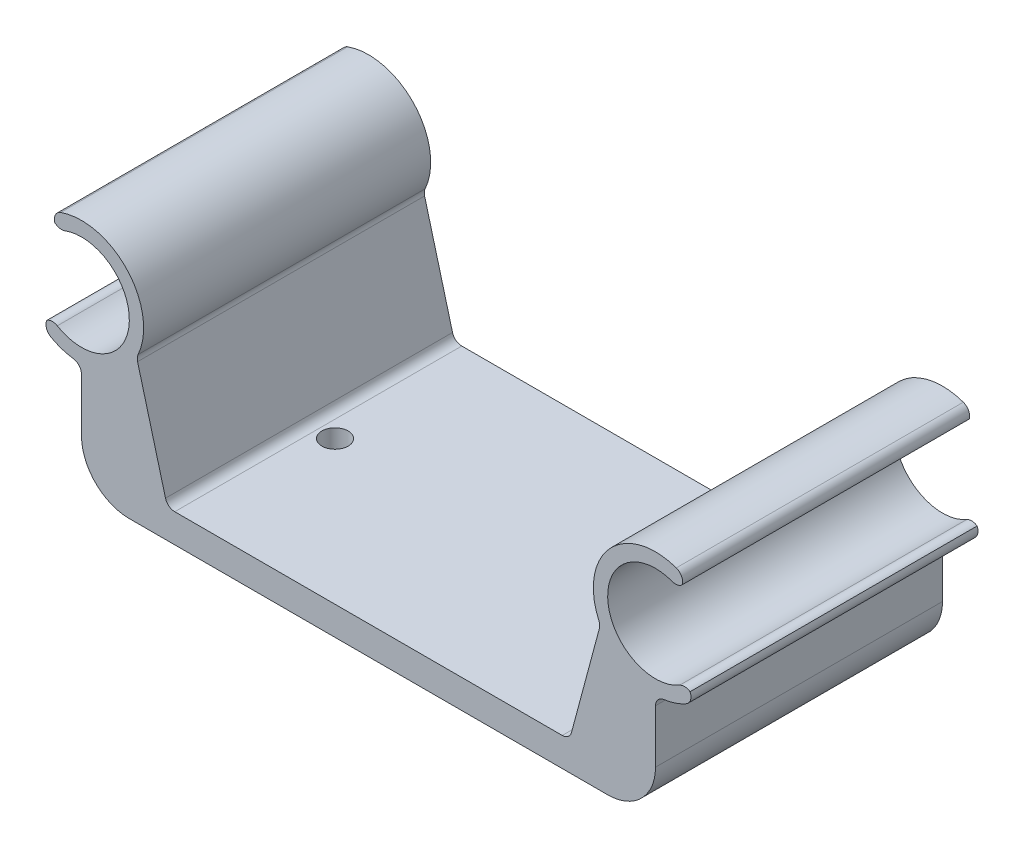
SolidWorks part; units mm, degrees
ref_plane "Front Plane" through (0, 0, 0) normal (0, 0, 1) x (1, 0, 0)
ref_plane "Top Plane" through (0, 0, 0) normal (0, 1, 0) x (1, 0, 0)
ref_plane "Right Plane" through (0, 0, 0) normal (1, 0, 0) x (0, 0, -1)
sketch "Sketch1" plane through (0, 0, 0) normal (0, 1, 0) x (1, 0, 0)
  line L1 (30, -15) -> (-30, -15)
  line L2 (30, -15) -> (30, 15)
  line L3 (30, 15) -> (-30, 15)
  line L4 (-30, -15) -> (-30, 15)
  line L5 (30, -15) -> (-30, 15) construction
  line L6 (30, 15) -> (-30, -15) construction
  point P0 (0, 0)
  dimension "D1" = 60
  dimension "0" = 30
extrude "Boss-Extrude1" add sketch "Sketch1" along normal blind 3
sketch "Sketch2" plane through (0, 3, 0) normal (0, 1, 0) x (1, 0, 0)
  line L0 (-30, 0) -> (0, 0) construction
  line L1 (-30, 15) -> (-30, -15) construction
  circle A0 centre (-18.5, 0) radius 1.375
  dimension "D1" = 2.75
  dimension "D2" = 18.5
extrude "Cut-Extrude1" cut sketch "Sketch2" against normal up to next
mirror "Mirror1" about plane through (0, 0, 0) normal (1, 0, 0) of "Cut-Extrude1"
sketch "Sketch3" plane through (0, 0, 0) normal (0, 0, 1) x (1, 0, 0)
  line L0 (-30, 3) -> (30, 3) construction
  line L1 (24.2337, 15) -> (21.0183, 3)
  line L2 (33.25, 23.6292) -> (32.5, 22.3301)
  line L3 (21.0183, 3) -> (30, 3)
  line L4 (33.2139, 14.1698) -> (34.1781, 13.0207)
  line L6 (30, 11.5) -> (30, 3)
  arc A1 (32.5, 22.3301) -> (33.2139, 14.1698) centre (30, 18) ccw
  arc A2 (24.2337, 15) -> (33.25, 23.6292) centre (30, 18) cw
  arc A3 (34.1781, 13.0207) -> (30, 11.5) centre (30, 18) cw
  dimension "D1" = 1.5
  dimension "D2" = 5
  dimension "D6" = 1.5
  dimension "D3" = 15
  dimension "D4" = 1.5
  dimension "D5" = 1.5
  dimension "D7" = 60
  dimension "D8" = 110
  dimension "D10" = 75
  dimension "D11" = 12
  dimension "D12" = 30
extrude "Boss-Extrude2" add sketch "Sketch3" along normal up to surface and the other way up to surface up to face at (0, 1.5, 15) other way up to face at (0, 1.5, -15)
fillet "Fillet3" radius 1 5 edges at (33.25, 23.6292, 0) (32.5, 22.3301, 0) (34.1781, 13.0207, 0) (33.2139, 14.1698, 0) (30, 11.5, 0)
mirror "Mirror2" about plane through (0, 0, 0) normal (1, 0, 0) of "Fillet3", "Boss-Extrude2"
fillet "Fillet6" radius 5 2 edges at (30, 0, 0) (-30, 0, 0)
fillet "Fillet7" radius 1 4 edges at (21.0183, 3, 0) (-21.0183, 3, 0) (24.2337, 15, 0) (-24.2337, 15, 0)
